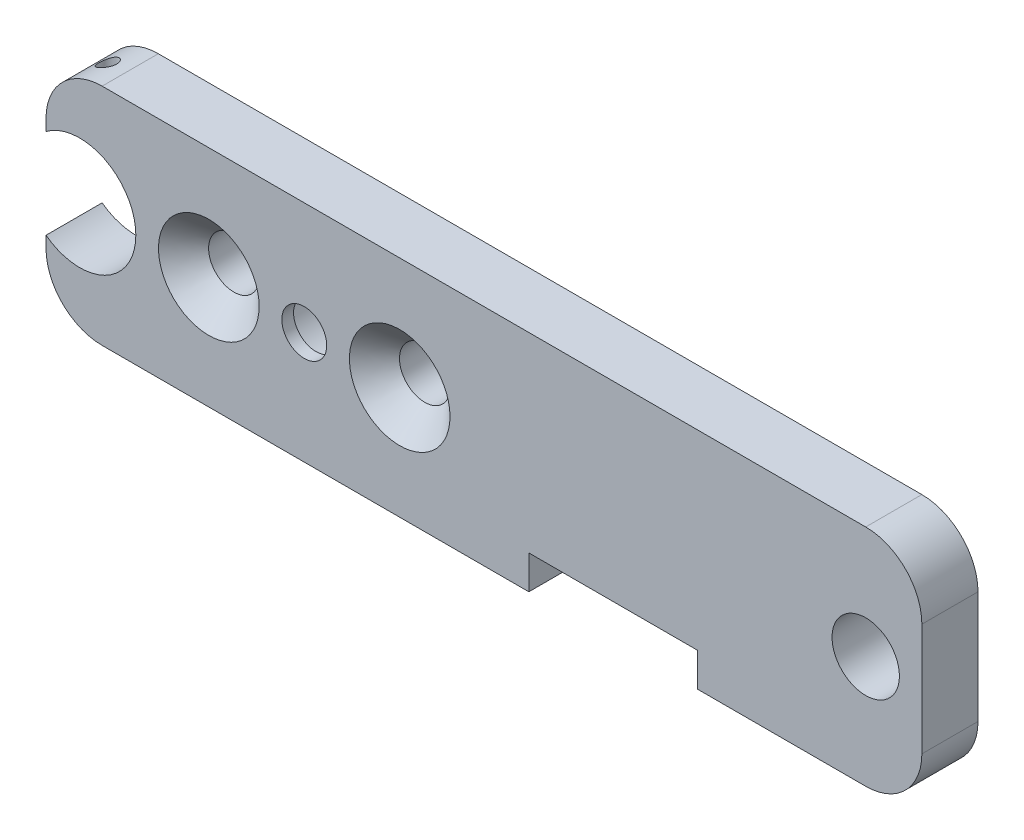
SolidWorks part; units mm, degrees
ref_plane "Front Plane" through (0, 0, 0) normal (0, 0, 1) x (1, 0, 0)
ref_plane "Top Plane" through (0, 0, 0) normal (0, 1, 0) x (1, 0, 0)
ref_plane "Right Plane" through (0, 0, 0) normal (1, 0, 0) x (0, 0, -1)
sketch "Sketch1" plane through (0, 0, 0) normal (0, 0, 1) x (1, 0, 0)
  line L1 (-27.303, 7.4194) -> (50.697, 7.4194)
  line L2 (-27.303, 7.4194) -> (-27.303, -12.5806)
  line L3 (-27.303, -12.5806) -> (50.697, -12.5806)
  line L4 (50.697, 7.4194) -> (50.697, -12.5806)
  dimension "D1" = 78
  dimension "D2" = 20
extrude "Boss-Extrude1" add sketch "Sketch1" along normal blind 5
sketch "Sketch2" plane through (0, 0, 5) normal (0, 0, 1) x (1, 0, 0)
  line L0 (-24.303, -2.5806) -> (-4.303, -2.5806) construction
  line L1 (-27.303, 7.4194) -> (-27.303, -12.5806) construction
  line L2 (-4.303, -2.5806) -> (-10.3134, -8.591) construction
  line L3 (-27.303, -2.5806) -> (-24.303, -2.5806) construction
  line L4 (-4.303, -2.5806) -> (-12.803, -2.5806) construction
  line L5 (-4.303, -2.5806) -> (1.7074, 3.4298) construction
  line L6 (-4.303, -2.5806) -> (4.197, -2.5806) construction
  line L7 (50.697, -2.5806) -> (45.697, -2.5806) construction
  line L8 (50.697, -12.5806) -> (50.697, 7.4194) construction
  dimension "D6" = 8.5
  dimension "D1" = 3
  dimension "D2" = 20
  dimension "D3" = 8.5
  dimension "D4" = 8.5
  dimension "D5" = 8.5
  dimension "D7" = 5
hole_wizard "Ø10.0mm Dowel Hole1" positions "3DSketch2" profile "Sketch4" hole size "Ø10.0" standard "ISO"
sketch3d "3DSketch2"
  point P0 (-24.303, -2.5806, 5)
sketch "Sketch4" plane through (-24.303, -2.5806, 5) normal (1, 0, 0) x (0, -1, 0)
  line L0 (0, 0) -> (0, 28.0043)
  line L1 (0, 28.0043) -> (5, 25)
  line L2 (5, 25) -> (5, 0)
  line L5 (5, 0) -> (0, 0)
  line L10 (0, 28.0043) -> (-5, 25) construction
  line L11 (0, -6.35) -> (0, 107.95) construction
  dimension "Hole Dia." = 10
  dimension "Hole Depth" = 25
  dimension "Drill Angle" = 118
hole_wizard "CSK for M4 Hex Socket Countersunk Cap Screw1" positions "3DSketch5" profile "Sketch8" countersink size "M4" standard "ISO" end condition through all
sketch3d "3DSketch5"
  point P0 (-12.803, -2.5806, 5)
  point P3 (4.197, -2.5806, 5)
sketch "Sketch8" plane through (-12.803, -2.5806, 5) normal (1, 0, 0) x (0, -1, 0)
  line L0 (0, 0) -> (0, 5)
  line L1 (0, 5) -> (2.25, 5)
  line L2 (2.25, 5) -> (2.25, 2.23)
  line L3 (2.25, 2.23) -> (4.48, 0)
  line L5 (4.48, 0) -> (0, 0)
  line L6 (-2.25, 2.23) -> (-4.48, 0) construction
  line L11 (0, -6.35) -> (0, 107.95) construction
  dimension "Thru Hole Dia." = 4.5
  dimension "Thru Hole Depth" = 5
  dimension "Near C'Sink Dia." = 8.96
  dimension "Near C'Sink Angle" = 90
hole_wizard "Ø6.0mm Dowel Hole1" positions "3DSketch6" profile "Sketch9" hole size "Ø6.0" standard "ISO"
sketch3d "3DSketch6"
  point P0 (45.697, -2.5806, 5)
sketch "Sketch9" plane through (45.697, -2.5806, 5) normal (1, 0, 0) x (0, -1, 0)
  line L0 (0, 0) -> (0, 26.8026)
  line L1 (0, 26.8026) -> (3, 25)
  line L2 (3, 25) -> (3, 0)
  line L5 (3, 0) -> (0, 0)
  line L10 (0, 26.8026) -> (-3, 25) construction
  line L11 (0, -6.35) -> (0, 107.95) construction
  dimension "Hole Dia." = 6
  dimension "Hole Depth" = 25
  dimension "Drill Angle" = 118
sketch "Sketch11" plane through (0, 0, 0) normal (0, 0, -1) x (-1, 0, 0)
  line L0 (4.303, -2.5806) -> (4.303, -6.9847) construction
hole_wizard "Ø4.0mm Dowel Hole2" positions "3DSketch8" profile "Sketch13" hole size "Ø4.0" standard "ISO"
sketch3d "3DSketch8"
  point P0 (-4.303, -2.5806, 0)
sketch "Sketch13" plane through (-4.303, -2.5806, 0) normal (1, 0, 0) x (0, 1, 0)
  line L0 (0, 0) -> (0, 26.2017)
  line L1 (0, 26.2017) -> (2, 25)
  line L2 (2, 25) -> (2, 0)
  line L5 (2, 0) -> (0, 0)
  line L10 (0, 26.2017) -> (-2, 25) construction
  line L11 (0, -6.35) -> (0, 107.95) construction
  dimension "Hole Dia." = 4
  dimension "Hole Depth" = 25
  dimension "Drill Angle" = 118
hole_wizard "Ø8.0mm Dowel Hole1" positions "3DSketch9" profile "Sketch14" hole size "Ø8.0" standard "ISO"
sketch3d "3DSketch9"
  point P0 (-4.303, -2.5806, 0)
sketch "Sketch14" plane through (-4.303, -2.5806, 0) normal (1, 0, 0) x (0, 1, 0)
  line L0 (0, 0) -> (0, 5.1534)
  line L1 (0, 5.1534) -> (4, 2.75)
  line L2 (4, 2.75) -> (4, 0)
  line L5 (4, 0) -> (0, 0)
  line L10 (0, 5.1534) -> (-4, 2.75) construction
  line L11 (0, -6.35) -> (0, 107.95) construction
  dimension "Hole Dia." = 8
  dimension "Hole Depth" = 2.75
  dimension "Drill Angle" = 118
fillet "Fillet1" radius 5 4 edges at (50.697, 7.4194, 2.5) (50.697, -12.5806, 2.5) (-27.303, -12.5806, 2.5) (-27.303, 7.4194, 2.5)
sketch "Sketch18" plane through (0, 0, 5) normal (0, 0, 1) x (1, 0, 0)
  line L2 (-22.303, 7.4194) -> (-28.3961, 7.4194) construction
  line L3 (-24.303, -2.5806) -> (-24.303, 7.4194) construction
sketch "Sketch19" plane through (0, 7.4194, 0) normal (0, 1, 0) x (1, 0, 0)
  line L0 (-24.303, -5) -> (-24.303, 0) construction
  line L1 (-24.303, -2.5) -> (-19.5848, -2.5) construction
hole_wizard "M2 Tapped Hole1" positions "3DSketch10" profile "Sketch20" tap size "M2" standard "ISO"
sketch3d "3DSketch10"
  point P0 (-24.303, 7.4194, 2.5)
sketch "Sketch20" plane through (-24.303, 7.4194, 2.5) normal (1, 0, 0) x (0, 0, 1)
  line L0 (0, 0) -> (0, 7.4807)
  line L1 (0, 7.4807) -> (0.8, 7)
  line L2 (0.8, 7) -> (0.8, 0)
  line L5 (0.8, 0) -> (0, 0)
  line L10 (0, 7.4807) -> (-0.8, 7) construction
  line L11 (0, -6.35) -> (0, 107.95) construction
  dimension "Tap Drill Dia." = 1.6
  dimension "Tap Drill Depth" = 7
  dimension "Drill Angle" = 118
sketch "Sketch22" plane through (0, 0, 0) normal (0, 0, -1) x (-1, 0, 0)
  line L0 (-50.697, -2.5806) -> (-30.697, -2.5806) construction
  line L1 (-30.697, -2.5806) -> (-30.697, -12.5806) construction
  line L2 (22.303, -12.5806) -> (-45.697, -12.5806) construction
  line L3 (-30.697, -12.5806) -> (-30.697, -9.5806)
  line L4 (-30.697, -9.5806) -> (-15.697, -9.5806)
  line L5 (-15.697, -9.5806) -> (-15.697, -12.5806)
  line L6 (-15.697, -12.5806) -> (-30.697, -12.5806)
  dimension "D1" = 20
  dimension "D2" = 3
  dimension "D3" = 15
extrude "Cut-Extrude1" cut sketch "Sketch22" against normal blind 10
sketch "Sketch23" plane through (0, 0, 0) normal (0, 0, -1) x (-1, 0, 0)
  circle A0 centre (4.303, -2.5806) radius 12.5
  circle A1 centre (24.303, -2.5806) radius 5
  dimension "D1" = 25
  dimension "D2" = 10
sketch "Sketch25" plane through (0, -9.5806, 0) normal (0, -1, 0) x (1, 0, 0)
  line L0 (30.697, 2.5) -> (15.697, 2.5) construction
  line L1 (30.697, 5) -> (30.697, 0) construction
  line L2 (15.697, 5) -> (15.697, 0) construction
  line L3 (23.197, 2.5) -> (23.197, 5) construction
  line L4 (30.697, 5) -> (15.697, 5) construction
hole_wizard "M2 Tapped Hole2" positions "3DSketch12" profile "Sketch26" tap size "M2" standard "ISO"
sketch3d "3DSketch12"
  point P0 (23.197, -9.5806, 2.5)
sketch "Sketch26" plane through (23.197, -9.5806, 2.5) normal (1, 0, 0) x (0, 0, -1)
  line L0 (0, 0) -> (0, 7.4807)
  line L1 (0, 7.4807) -> (0.8, 7)
  line L2 (0.8, 7) -> (0.8, 0)
  line L5 (0.8, 0) -> (0, 0)
  line L10 (0, 7.4807) -> (-0.8, 7) construction
  line L11 (0, -6.35) -> (0, 107.95) construction
  dimension "Tap Drill Dia." = 1.6
  dimension "Tap Drill Depth" = 7
  dimension "Drill Angle" = 118
cosmetic thread "Hole Thread1" parameters "D1"=5, "D2"=2
